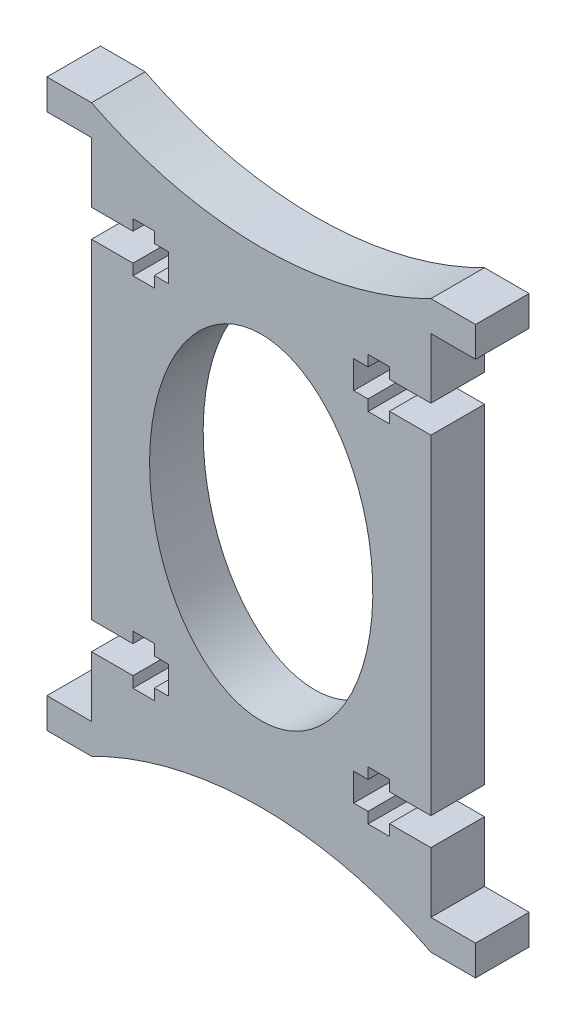
SolidWorks part; units mm, degrees
material "Acrylic (Medium-high impact)"
ref_plane "Front Plane" through (0, 0, 0) normal (0, 0, 1) x (1, 0, 0)
ref_plane "Top Plane" through (0, 0, 0) normal (0, 1, 0) x (1, 0, 0)
ref_plane "Right Plane" through (0, 0, 0) normal (1, 0, 0) x (0, 0, -1)
sketch "Sketch1" plane through (0, 0, 0) normal (0, 0, 1) x (1, 0, 0)
  line L0 (740.5185, 459.4261) -> (702.5185, 459.4261) construction
  line L1 (735.8803, 439.4261) -> (740.5185, 439.4261) construction
  line L2 (735.8803, 439.4261) -> (735.8803, 437.8782) construction
  line L3 (735.8803, 440.9739) -> (735.8803, 439.4261) construction
  line L4 (734.6803, 436.6538) -> (734.6803, 439.4261) construction
  line L5 (731.8803, 439.4261) -> (740.5185, 439.4261) construction
  line L6 (734.6803, 442.1983) -> (734.6803, 439.4261) construction
  line L7 (733.4803, 436.6538) -> (735.8803, 436.6538)
  line L8 (702.5185, 459.4261) -> (702.5185, 440.9739)
  line L9 (708.3567, 442.1983) -> (708.3567, 439.4261) construction
  line L10 (733.4803, 442.1983) -> (735.8803, 442.1983)
  line L11 (731.8803, 440.9739) -> (731.8803, 437.8782)
  line L12 (740.5185, 437.8782) -> (740.5185, 431.1161)
  line L13 (740.5185, 437.8782) -> (735.8803, 437.8782)
  line L14 (735.8803, 440.9739) -> (740.5185, 440.9739)
  line L15 (745.5185, 427.7361) -> (745.5185, 431.1161)
  line L16 (740.5185, 427.7361) -> (745.5185, 427.7361)
  line L17 (711.1567, 439.4261) -> (702.5185, 439.4261) construction
  line L18 (709.5567, 436.6538) -> (709.5567, 437.8782)
  line L19 (709.5567, 440.9739) -> (711.1567, 440.9739)
  line L20 (709.5567, 437.8782) -> (711.1567, 437.8782)
  line L21 (709.5567, 440.9739) -> (709.5567, 442.1983)
  line L22 (708.3567, 436.6538) -> (708.3567, 439.4261) construction
  line L23 (707.1567, 436.6538) -> (707.1567, 437.8782)
  line L24 (707.1567, 440.9739) -> (707.1567, 442.1983)
  line L25 (707.1567, 440.9739) -> (707.1567, 439.4261) construction
  line L26 (707.1567, 439.4261) -> (707.1567, 437.8782) construction
  line L27 (697.5185, 431.1161) -> (702.5185, 431.1161)
  line L28 (702.5185, 427.7361) -> (697.5185, 427.7361)
  line L29 (697.5185, 427.7361) -> (697.5185, 431.1161)
  line L30 (707.1567, 440.9739) -> (702.5185, 440.9739)
  line L31 (702.5185, 437.8782) -> (707.1567, 437.8782)
  line L32 (702.5185, 437.8782) -> (702.5185, 431.1161)
  line L33 (707.1567, 439.4261) -> (702.5185, 439.4261) construction
  line L34 (711.1567, 440.9739) -> (711.1567, 437.8782)
  line L35 (745.5185, 431.1161) -> (740.5185, 431.1161)
  line L36 (735.8803, 440.9739) -> (735.8803, 442.1983)
  line L37 (735.8803, 436.6538) -> (735.8803, 437.8782)
  line L38 (733.4803, 440.9739) -> (733.4803, 442.1983)
  line L39 (733.4803, 437.8782) -> (731.8803, 437.8782)
  line L40 (733.4803, 440.9739) -> (731.8803, 440.9739)
  line L41 (733.4803, 436.6538) -> (733.4803, 437.8782)
  line L42 (740.5185, 459.4261) -> (740.5185, 440.9739)
  line L43 (707.1567, 479.4261) -> (702.5185, 479.4261) construction
  line L44 (709.5567, 442.1983) -> (707.1567, 442.1983)
  line L45 (707.1567, 479.4261) -> (707.1567, 480.9739) construction
  line L46 (707.1567, 477.8782) -> (707.1567, 479.4261) construction
  line L47 (708.3567, 482.1983) -> (708.3567, 479.4261) construction
  line L48 (711.1567, 479.4261) -> (702.5185, 479.4261) construction
  line L49 (708.3567, 476.6538) -> (708.3567, 479.4261) construction
  line L50 (734.6803, 476.6538) -> (734.6803, 479.4261) construction
  line L51 (731.8803, 479.4261) -> (740.5185, 479.4261) construction
  line L52 (734.6803, 482.1983) -> (734.6803, 479.4261) construction
  line L53 (735.8803, 477.8782) -> (735.8803, 479.4261) construction
  line L54 (735.8803, 479.4261) -> (735.8803, 480.9739) construction
  line L55 (735.8803, 479.4261) -> (740.5185, 479.4261) construction
  line L56 (709.5567, 482.1983) -> (707.1567, 482.1983)
  line L57 (709.5567, 476.6538) -> (707.1567, 476.6538)
  line L58 (740.5185, 459.4261) -> (740.5185, 477.8782)
  line L59 (733.4803, 482.1983) -> (733.4803, 480.9739)
  line L60 (721.5185, -540.5691) -> (721.5185, 49459.4309) construction
  line L61 (709.5567, 436.6538) -> (707.1567, 436.6538)
  line L62 (733.4803, 477.8782) -> (731.8803, 477.8782)
  line L63 (733.4803, 480.9739) -> (731.8803, 480.9739)
  line L64 (733.4803, 477.8782) -> (733.4803, 476.6538)
  line L65 (735.8803, 482.1983) -> (735.8803, 480.9739)
  line L66 (735.8803, 477.8782) -> (735.8803, 476.6538)
  line L67 (745.5185, 487.7361) -> (740.5185, 487.7361)
  line L68 (711.1567, 477.8782) -> (711.1567, 480.9739)
  line L69 (702.5185, 480.9739) -> (702.5185, 487.7361)
  line L70 (702.5185, 480.9739) -> (707.1567, 480.9739)
  line L71 (707.1567, 477.8782) -> (702.5185, 477.8782)
  line L72 (697.5185, 491.1161) -> (697.5185, 487.7361)
  line L73 (702.5185, 491.1161) -> (697.5185, 491.1161)
  line L74 (697.5185, 487.7361) -> (702.5185, 487.7361)
  line L75 (707.1567, 477.8782) -> (707.1567, 476.6538)
  line L76 (707.1567, 482.1983) -> (707.1567, 480.9739)
  line L77 (709.5567, 477.8782) -> (709.5567, 476.6538)
  line L78 (709.5567, 480.9739) -> (711.1567, 480.9739)
  line L79 (709.5567, 477.8782) -> (711.1567, 477.8782)
  line L80 (709.5567, 482.1983) -> (709.5567, 480.9739)
  line L81 (740.5185, 491.1161) -> (745.5185, 491.1161)
  line L82 (745.5185, 491.1161) -> (745.5185, 487.7361)
  line L83 (735.8803, 477.8782) -> (740.5185, 477.8782)
  line L84 (740.5185, 480.9739) -> (735.8803, 480.9739)
  line L85 (740.5185, 480.9739) -> (740.5185, 487.7361)
  line L86 (731.8803, 477.8782) -> (731.8803, 480.9739)
  line L87 (733.4803, 476.6538) -> (735.8803, 476.6538)
  line L88 (702.5185, 459.4261) -> (702.5185, 477.8782)
  line L89 (733.4803, 482.1983) -> (735.8803, 482.1983)
  line L90 (721.5185, 459.4261) -> (708.0185, 459.4261) construction
  line L91 (702.5185, 480.9739) -> (702.5185, 477.8782) construction
  line L92 (702.5185, 487.7361) -> (702.5185, 491.1161) construction
  line L93 (702.5185, 431.1161) -> (702.5185, 427.7361) construction
  line L94 (702.5185, 491.1161) -> (740.5185, 491.1161) construction
  line L95 (702.5185, 427.7361) -> (740.5185, 427.7361) construction
  line L96 (740.5185, 480.9739) -> (740.5185, 477.8782) construction
  line L97 (740.5185, 440.9739) -> (740.5185, 437.8782) construction
  arc A0 (702.5185, 491.1161) -> (740.5185, 491.1161) centre (721.5185, 528.5727) ccw
  arc A1 (702.5185, 427.7361) -> (740.5185, 427.7361) centre (721.5185, 390.2794) cw
  ellipse E0 centre (721.5185, 459.4261) end of major axis (721.5185, 478.1761) minor radius 12.5
  point P30 (721.5185, 478.1761)
  point P38 (721.5185, 459.4261)
  point P102 (702.5185, 489.4261)
  point P103 (702.5185, 429.4261)
  point P105 (721.5185, 440.6761)
  dimension "D9" = 42
  dimension "D1" = 60
  dimension "D2" = 3.0957
  dimension "D3" = 3.38
  dimension "D4" = 10
  dimension "D5" = 1.6
  dimension "D6" = 38
  dimension "D7" = 2.4
  dimension "D8" = 1.2244
  dimension "D10" = 5
  dimension "D11" = 18.75
  dimension "D12" = 25
  dimension "D15" = 4.6382
extrude "Boss-Extrude1" add sketch "Sketch1" along normal blind 6
